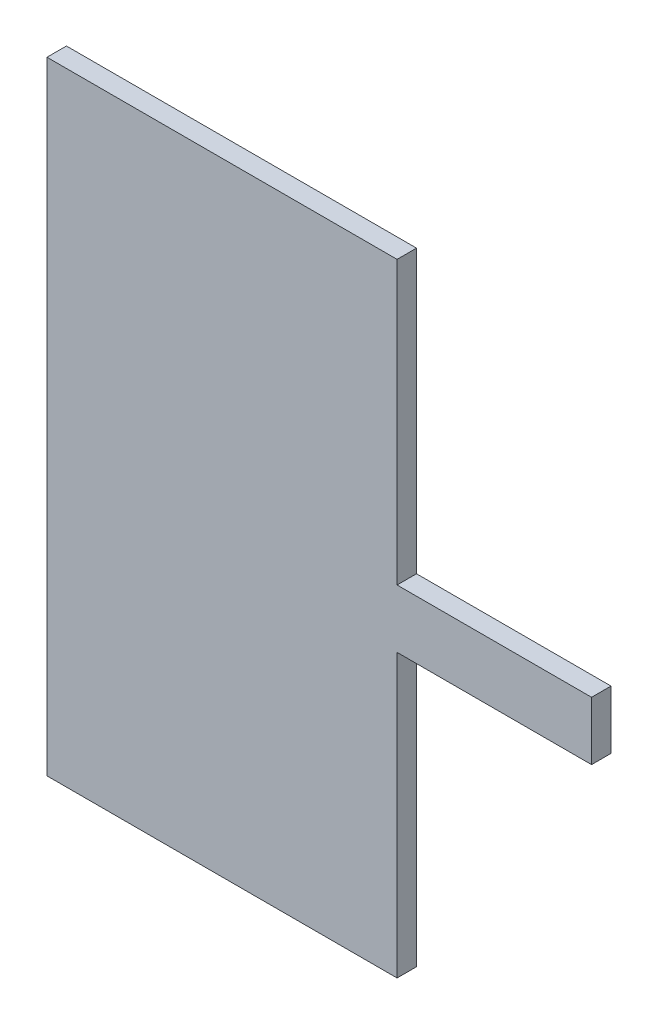
SolidWorks part; units mm, degrees
material "6061-T4 (SS)"
ref_plane "Front Plane" through (0, 0, 0) normal (0, 0, 1) x (1, 0, 0)
ref_plane "Top Plane" through (0, 0, 0) normal (0, 1, 0) x (1, 0, 0)
ref_plane "Right Plane" through (0, 0, 0) normal (1, 0, 0) x (0, 0, -1)
sketch "Sketch1" plane through (0, 0, 0) normal (0, 0, 1) x (1, 0, 0)
  line L3 (15.5494, 25) -> (29.7363, 25) construction
  line L6 (29.7363, -7) -> (11.7363, -7)
  line L7 (29.7363, 7.5) -> (39.7363, 7.5)
  line L8 (39.7363, 7.5) -> (39.7363, 10.5)
  line L9 (39.7363, 10.5) -> (29.7363, 10.5)
  line L10 (29.7363, -7) -> (29.7363, 7.5)
  line L11 (29.7363, 10.5) -> (29.7363, 25)
  line L12 (11.7363, -7) -> (11.7363, 25)
  line L13 (11.7363, 25) -> (29.7363, 25)
  dimension "D1" = 3
  dimension "D2" = 14.5
  dimension "D3" = 10
  dimension "D4" = 18
  dimension "D5" = 32
extrude "Boss-Extrude1" add sketch "Sketch1" along normal blind 1
